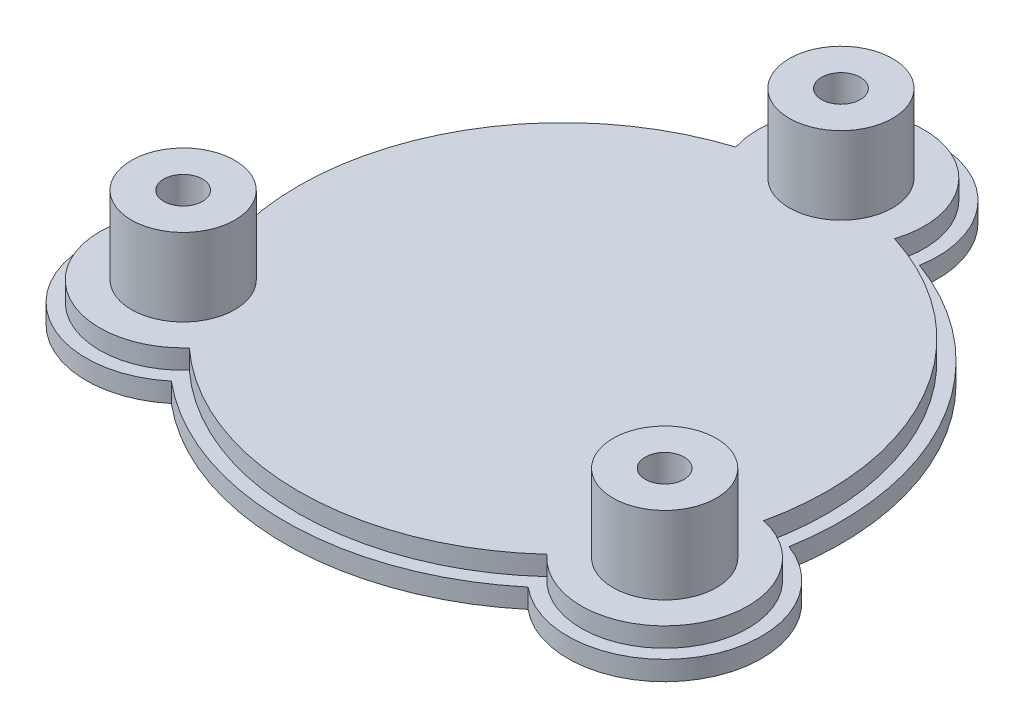
SolidWorks part; units mm, degrees
ref_plane "Front Plane" through (0, 0, 0) normal (0, 0, 1) x (1, 0, 0)
ref_plane "Top Plane" through (0, 0, 0) normal (0, 1, 0) x (1, 0, 0)
ref_plane "Right Plane" through (0, 0, 0) normal (1, 0, 0) x (0, 0, -1)
sketch "Sketch1" plane through (0, 0, 0) normal (0, 1, 0) x (1, 0, 0)
  circle A0 centre (0, 0) radius 43
  circle A1 centre (0, 43) radius 15
  circle A2 centre (0, 43) radius 6
  circle A3 centre (37.2391, -21.5) radius 15
  circle A4 centre (37.2391, -21.5) radius 6
  circle A5 centre (-37.2391, -21.5) radius 15
  circle A6 centre (-37.2391, -21.5) radius 6
  circle A7 centre (0, 43) radius 8
  circle A8 centre (37.2391, -21.5) radius 8
  circle A9 centre (-37.2391, -21.5) radius 8
  point P15 (0, 0)
  point P21 (0, 0)
  dimension "D1" = 86
  dimension "D2" = 30
  dimension "D3" = 12
  dimension "D5" = 16
  dimension "D4" = 3
  dimension "D6" = 3
extrude "Boss-Extrude1" add sketch "Sketch1" along normal blind 3 contours A6 A0 A5 | A6 A0 A5 | A5 A0 A3 A1 | A4 A0 A3 | A4 A0 A3 | A2 A0 A1 | A1 | A2 | A9 | A6 | A8 | A4 region at (0, 0, 0) region at (11.4984, 0, -41.795) region at (49.2107, 0, 13.1104) region at (30.1461, 0, 17.4049) region at (-30.1461, 0, 17.4049) region at (-41.9772, 0, 10.948)
extrude "Boss-Extrude2" add sketch "Sketch1<3>" along normal blind 18 contours A0 A9 A6 | A0 A9 A6 | A0 A8 A4 | A0 A8 A4 | A0 A7 A2 | A0 A7 A2 region at (0, 0, -35.1764) region at (7.0068, 0, -42.6101) region at (43.8067, 0, 17.2887) region at (40.0618, 0, 15.1076) region at (-33.0203, 0, 14.9207) region at (-40.4196, 0, 15.2425)
sketch "Sketch1<3>" plane through (0, 0, 0) normal (0, 1, 0) x (1, 0, 0) same geometry as "Sketch1"
sketch "Sketch2" plane through (0, 3, 0) normal (0, 1, 0) x (1, 0, 0)
  arc A0 (-12.2695, 39.0163) -> (-39.9238, -8.8825) centre (0, 0) ccw
  arc A1 (-39.9238, -8.8825) -> (-27.6544, -30.1338) centre (-37.2391, -21.5) ccw
  arc A2 (-27.6544, -30.1338) -> (27.6544, -30.1338) centre (0, 0) ccw
  arc A3 (27.6544, -30.1338) -> (39.9238, -8.8825) centre (37.2391, -21.5) ccw
  arc A4 (39.9238, -8.8825) -> (12.2695, 39.0163) centre (0, 0) ccw
  arc A5 (12.2695, 39.0163) -> (-12.2695, 39.0163) centre (0, 43) ccw
  arc A6 (27.5883, -32.9831) -> (42.3584, -7.4006) centre (37.2391, -21.5) ccw
  arc A7 (42.3584, -7.4006) -> (14.7701, 40.3837) centre (0, 0) ccw
  arc A8 (14.7701, 40.3837) -> (-14.7701, 40.3837) centre (0, 43) ccw
  arc A9 (-14.7701, 40.3837) -> (-42.3584, -7.4006) centre (0, 0) ccw
  arc A10 (-42.3584, -7.4006) -> (-27.5883, -32.9831) centre (-37.2391, -21.5) ccw
  arc A11 (-27.5883, -32.9831) -> (27.5883, -32.9831) centre (0, 0) ccw
  arc A12 (27.5883, -32.9831) -> (42.3584, -7.4006) centre (37.2391, -21.5) ccw
  arc A13 (42.3584, -7.4006) -> (14.7701, 40.3837) centre (0, 0) ccw
  arc A14 (14.7701, 40.3837) -> (-14.7701, 40.3837) centre (0, 43) ccw
  arc A15 (-14.7701, 40.3837) -> (-42.3584, -7.4006) centre (0, 0) ccw
  arc A16 (-42.3584, -7.4006) -> (-27.5883, -32.9831) centre (-37.2391, -21.5) ccw
  arc A17 (-27.5883, -32.9831) -> (27.5883, -32.9831) centre (0, 0) ccw
  circle M13 centre (37.2391, -21.5) radius 8
  circle M14 centre (-37.2391, -21.5) radius 8
  circle M21 centre (0, 43) radius 8
  dimension "D1" = 0
  dimension "D2" = 2.1
extrude "Boss-Extrude3" add sketch "Sketch2" along normal blind 3 contours A4 A5 A0 A1 A2 A3 M13 M21 M14 region at (0, 3, 0)
sketch "Sketch3" plane through (0, 18, 0) normal (0, 1, 0) x (1, 0, 0)
  circle A0 centre (-37.2391, -21.5) radius 6
  circle A1 centre (-37.2391, -21.5) radius 3
  circle A2 centre (0, 43) radius 3
  circle A3 centre (0, 43) radius 6
  circle A4 centre (37.2391, -21.5) radius 3
  circle A5 centre (37.2391, -21.5) radius 6
  point P12 (0, 0)
  dimension "D1" = 6
  dimension "D2" = 3
extrude "Boss-Extrude4" add sketch "Sketch3" against normal blind 6
